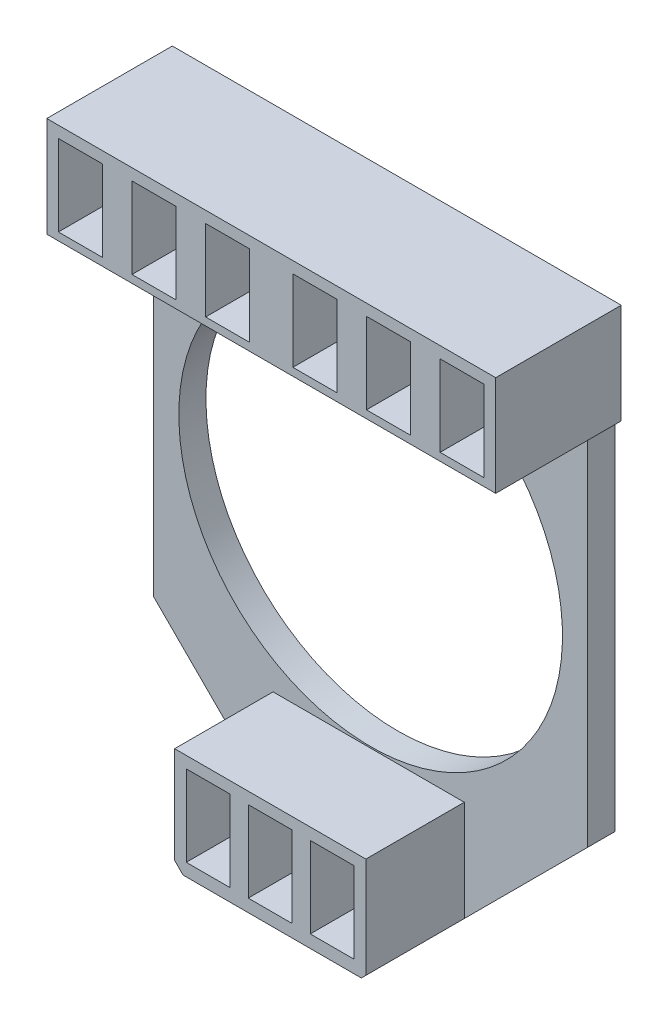
SolidWorks part; units mm, degrees
note: The reader was unsure of these and kept them because the rebuilt part matched: shared geometry of "Sketch2<3>".
ref_plane "Front Plane" through (0, 0, 0) normal (0, 0, 1) x (1, 0, 0)
ref_plane "Top Plane" through (0, 0, 0) normal (0, 1, 0) x (1, 0, 0)
ref_plane "Right Plane" through (0, 0, 0) normal (1, 0, 0) x (0, 0, -1)
sketch "Sketch2" plane through (0, 0, 0) normal (0, 0, 1) x (1, 0, 0)
  line L6 (-33.2302, 68.5904) -> (-33.2302, 53.5904)
  line L12 (-58.1817, 74.5) -> (57.6715, 74.5)
  line L25 (-58.1817, 74.5) -> (-58.1817, 48.6399)
  line L37 (-58.1817, 48.6399) -> (57.6715, 48.6399)
  line L46 (-56, 74.5) -> (-56, -44)
  line L50 (56, -44) -> (56, 74.5)
  line L51 (56, 74.5) -> (-56, 74.5)
  line L52 (-22.1817, -73.7409) -> (-10.8387, -73.7409)
  line L53 (-22.1817, -73.7409) -> (-22.1817, -52.8399)
  line L54 (-22.1817, -52.8399) -> (-10.8387, -52.8399)
  line L55 (-10.8387, -73.7409) -> (-10.8387, -52.8399)
  line L64 (-36.1817, 50.6399) -> (-24.8387, 50.6399)
  line L65 (-55.1817, 50.6399) -> (-43.8387, 50.6399)
  line L66 (-55.1817, 50.6399) -> (-55.1817, 71.5409)
  line L67 (-55.1817, 71.5409) -> (-43.8387, 71.5409)
  line L68 (-43.8387, 50.6399) -> (-43.8387, 71.5409)
  line L69 (-24.8387, 50.6399) -> (-24.8387, 71.5409)
  line L70 (-36.1817, 71.5409) -> (-24.8387, 71.5409)
  line L71 (-36.1817, 50.6399) -> (-36.1817, 71.5409)
  line L72 (-17.1817, 50.6399) -> (-5.8387, 50.6399)
  line L73 (-5.8387, 50.6399) -> (-5.8387, 71.5409)
  line L74 (-17.1817, 71.5409) -> (-5.8387, 71.5409)
  line L75 (-17.1817, 50.6399) -> (-17.1817, 71.5409)
  line L76 (43.3285, 50.6399) -> (54.6715, 50.6399)
  line L77 (43.3285, 50.6399) -> (43.3285, 71.5409)
  line L78 (43.3285, 71.5409) -> (54.6715, 71.5409)
  line L79 (54.6715, 50.6399) -> (54.6715, 71.5409)
  line L80 (24.3285, 50.6399) -> (35.6715, 50.6399)
  line L81 (35.6715, 50.6399) -> (35.6715, 71.5409)
  line L82 (24.3285, 71.5409) -> (35.6715, 71.5409)
  line L83 (24.3285, 50.6399) -> (24.3285, 71.5409)
  line L84 (5.3285, 50.6399) -> (16.6715, 50.6399)
  line L85 (16.6715, 50.6399) -> (16.6715, 71.5409)
  line L86 (5.3285, 71.5409) -> (16.6715, 71.5409)
  line L87 (5.3285, 50.6399) -> (5.3285, 71.5409)
  line L88 (57.6715, 74.5) -> (57.6715, 48.6399)
  line L93 (-52.2302, 68.5904) -> (-46.7902, 68.5904)
  line L94 (-52.2302, 68.5904) -> (-52.2302, 53.5904)
  line L95 (-52.2302, 53.5904) -> (-46.7902, 53.5904)
  line L96 (-46.7902, 68.5904) -> (-46.7902, 53.5904)
  line L97 (-33.2302, 68.5904) -> (-27.7902, 68.5904)
  line L98 (-27.7902, 68.5904) -> (-27.7902, 53.5904)
  line L99 (-33.2302, 53.5904) -> (-27.7902, 53.5904)
  line L100 (-14.2302, 68.5904) -> (-14.2302, 53.5904)
  line L101 (-14.2302, 68.5904) -> (-8.7902, 68.5904)
  line L102 (-8.7902, 68.5904) -> (-8.7902, 53.5904)
  line L103 (-14.2302, 53.5904) -> (-8.7902, 53.5904)
  line L104 (27.28, 68.5904) -> (27.28, 53.5904)
  line L105 (8.28, 68.5904) -> (13.72, 68.5904)
  line L106 (8.28, 68.5904) -> (8.28, 53.5904)
  line L107 (8.28, 53.5904) -> (13.72, 53.5904)
  line L108 (13.72, 68.5904) -> (13.72, 53.5904)
  line L109 (27.28, 68.5904) -> (32.72, 68.5904)
  line L110 (32.72, 68.5904) -> (32.72, 53.5904)
  line L111 (27.28, 53.5904) -> (32.72, 53.5904)
  line L112 (46.28, 68.5904) -> (46.28, 53.5904)
  line L113 (46.28, 68.5904) -> (51.72, 68.5904)
  line L114 (51.72, 68.5904) -> (51.72, 53.5904)
  line L115 (46.28, 53.5904) -> (51.72, 53.5904)
  line L116 (-3.2302, -55.7904) -> (-3.2302, -70.7904)
  line L117 (-19.2302, -55.7904) -> (-13.7902, -55.7904)
  line L118 (-19.2302, -55.7904) -> (-19.2302, -70.7904)
  line L119 (-19.2302, -70.7904) -> (-13.7902, -70.7904)
  line L120 (-13.7902, -55.7904) -> (-13.7902, -70.7904)
  line L121 (-3.2302, -55.7904) -> (2.2098, -55.7904)
  line L122 (2.2098, -55.7904) -> (2.2098, -70.7904)
  line L123 (-3.2302, -70.7904) -> (2.2098, -70.7904)
  line L124 (12.7698, -55.7904) -> (12.7698, -70.7904)
  line L125 (12.7698, -55.7904) -> (18.2098, -55.7904)
  line L126 (18.2098, -55.7904) -> (18.2098, -70.7904)
  line L127 (12.7698, -70.7904) -> (18.2098, -70.7904)
  line L128 (-6.1817, -73.7409) -> (5.1613, -73.7409)
  line L133 (5.1613, -73.7409) -> (5.1613, -52.8399)
  line L134 (-6.1817, -52.8399) -> (5.1613, -52.8399)
  line L135 (-6.1817, -73.7409) -> (-6.1817, -52.8399)
  line L136 (9.8183, -73.7409) -> (21.1613, -73.7409)
  line L137 (21.1613, -73.7409) -> (21.1613, -52.8399)
  line L138 (9.8183, -52.8399) -> (21.1613, -52.8399)
  line L139 (9.8183, -73.7409) -> (9.8183, -52.8399)
  line L140 (-56, -44) -> (-23, -77)
  line L141 (-23, -77) -> (23, -77)
  line L142 (23, -77) -> (56, -44)
  line L144 (-25.1817, -49.8399) -> (24.1613, -49.8399)
  line L145 (-25.1817, -49.8399) -> (-25.1817, -77)
  line L146 (-25.1817, -77) -> (24.1613, -77)
  line L147 (24.1613, -49.8399) -> (24.1613, -77)
  circle A2 centre (0, 0) radius 47.752
  circle A3 centre (0, 0) radius 49.5
  point P5 (-0.5102, -52.8399)
  point P6 (-16.5102, -52.8399)
  point P17 (-30.5102, 71.5409)
  point P18 (-30.5102, 68.5904)
  point P19 (-11.5102, 68.5904)
  point P20 (-11.5102, 71.5409)
  point P21 (30, 71.5409)
  point P22 (30, 68.5904)
  point P23 (49, 71.5409)
  point P24 (49, 68.5904)
  point P83 (-49.5102, 68.5904)
  point P94 (-16.5102, -55.7904)
  point P95 (-0.5102, -55.7904)
  point P96 (-16.5102, -70.7904)
  dimension "D6" = 95.504
  dimension "D7" = 99
  dimension "D1" = 11.343
  dimension "D2" = 20.901
  dimension "D8" = 56
  dimension "D9" = 74.5
  dimension "D10" = 112
  dimension "D11" = 118.5
  dimension "D23" = 2
  dimension "D29" = 5.44
  dimension "D30" = 15
  dimension "D31" = 2.9505
  dimension "D32" = 2.9515
  dimension "D35" = 2.9515
  dimension "D36" = 2.9505
  dimension "D39" = 2.9515
  dimension "D40" = 2.9505
  dimension "D5" = 6.4898
  dimension "D14" = 5.9096
  dimension "D15" = 19
  dimension "D16" = 7
  dimension "D17" = 19
  dimension "D18" = 16
  dimension "D21" = 3
  dimension "D22" = 3
  dimension "D25" = 16
  dimension "D12" = 46
  dimension "D13" = 135
  dimension "D19" = 135
  dimension "D20" = 6.2096
  dimension "D26" = 6.4898
  dimension "D27" = 3
  dimension "D28" = 3
  dimension "D34" = 3
  dimension "D33" = 3
  dimension "D37" = 3
  dimension "D41" = 3
  dimension "D24" = 3
extrude "Boss-Extrude1" add sketch "Sketch2" along normal blind 7
extrude "Boss-Extrude2" add sketch "Sketch2<3>" along normal blind 25.4 from surface at 7
sketch "Sketch2<3>" plane through (0, 0, 0) normal (0, 0, 1) x (1, 0, 0) same geometry as "Sketch2"
equation "\"D31@Sketch2\"=(\"D2@Sketch2\"-\"D30@Sketch2\")/2"
equation "\"D32@Sketch2\"=(\"D1@Sketch2\"-\"D29@Sketch2\")/2"
equation "\"D35@Sketch2\"=\"D32@Sketch2\""
equation "\"D36@Sketch2\"=\"D31@Sketch2\""
equation "\"D22@Sketch2\"=\"D21@Sketch2\""
equation "\"D14@Sketch2\"=6.45mm - (\"D30@Sketch2\"-13.9192)/2"
equation "\"D5@Sketch2\"=7.00mm - (\"D29@Sketch2\"-4.4196)/2"
equation "\"D26@Sketch2\"=\"D5@Sketch2\""
equation "\"D20@Sketch2\"= 6.75mm - (\"D30@Sketch2\"-13.9192)/2"
equation "\"D27@Sketch2\"=\"D22@Sketch2\""
equation "\"D28@Sketch2\"=\"D27@Sketch2\""
